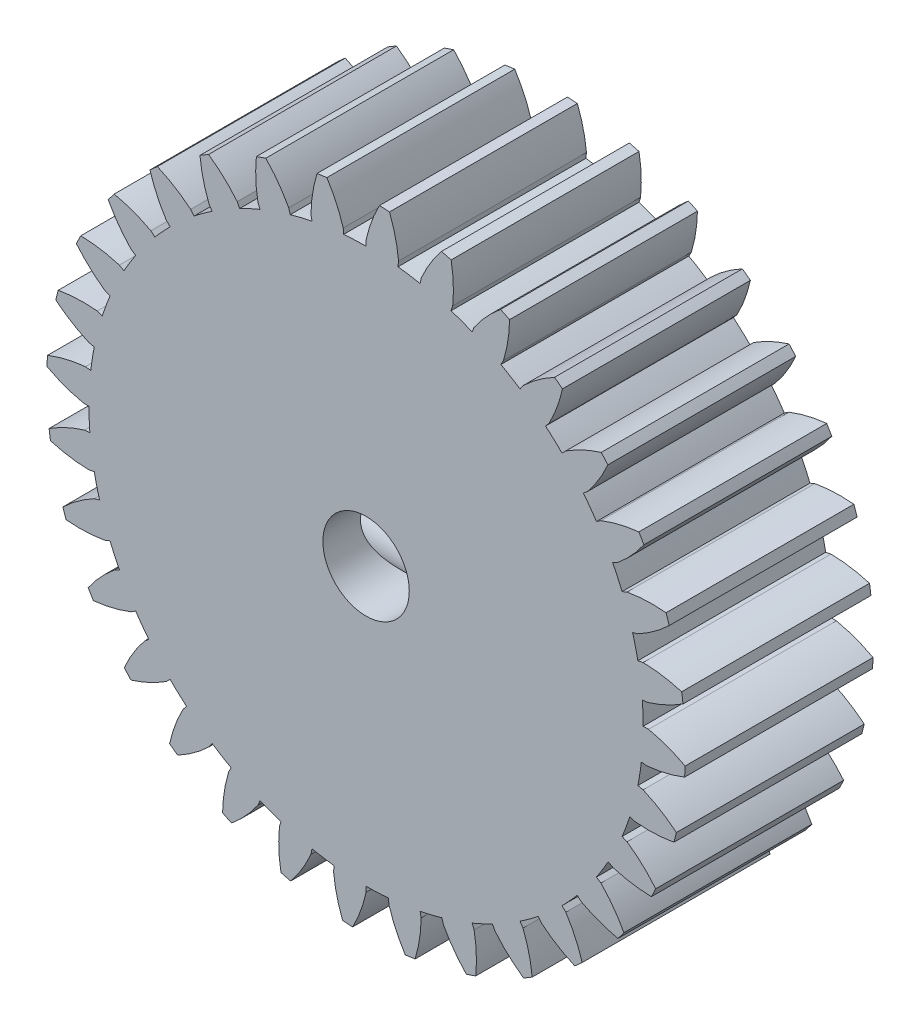
SolidWorks part; units mm, degrees
ref_plane "Front Plane" through (0, 0, 0) normal (0, 0, 1) x (1, 0, 0)
ref_plane "Top Plane" through (0, 0, 0) normal (0, 1, 0) x (1, 0, 0)
ref_plane "Right Plane" through (0, 0, 0) normal (1, 0, 0) x (0, 0, -1)
sketch "Gear" plane through (0, 0, 0) normal (0, 0, 1) x (1, 0, 0)
  circle A0 centre (0, 0) radius 8
  circle A1 centre (0, 0) radius 8.5
  circle A2 centre (0, 0) radius 7.375
  circle A3 centre (0, 0) radius 7.5
  circle A4 centre (0, 0) radius 7.5175
  dimension "Pitch" = 16
  dimension "Addendum" = 17
  dimension "Root" = 14.75
  dimension "Clearance" = 15
  dimension "Base" = 15.0351
sketch "Involute" plane through (0, 0, 0) normal (0, 0, 1) x (1, 0, 0)
  line L0 (0, 0) -> (0, 7.5175)
  line L1 (0, 0) -> (3.7588, 6.5104) construction
  line L2 (0, 0) -> (6.5104, 3.7588) construction
  line L3 (0, 0) -> (7.5175, 0) construction
  line L4 (7.5175, 0) -> (7.5175, 11.8085) construction
  line L5 (6.5104, 3.7588) -> (2.5742, 10.5764) construction
  line L6 (3.7588, 6.5104) -> (0.3499, 8.4785) construction
  line L7 (0, 0) -> (0.7841, 7.9615) construction
  line L8 (0, 0) -> (1.5607, 7.8463)
  line L9 (0.4614, 7.9867) -> (0, 0) construction
  circle A0 centre (0, 0) radius 7.5175 construction
  circle A1 centre (0, 0) radius 8 construction
  arc A3 (0.7841, 7.9615) -> (0.1378, 7.9988) centre (0, 0) ccw
  spline S0 degree 3 poles (0, 7.5175) (0.6613, 10.5961) (4.9807, 11.8125) (7.5175, 11.8085) knots 0 0 0 0 1 1 1 1
  spline S1 degree 3 poles (0.8656, 7.4675) (0.5632, 10.6018) (-3.5874, 12.3075) (-6.1078, 12.5956) knots 0 0 0 0 1 1 1 1
  point P10 (0, 0)
  dimension "Involute Control" = 90
  dimension "Base Circle Quarter Circumference" = 11.8085
  dimension "D1" = 7.8724
  dimension "D2" = 3.9362
  dimension "Circular Pitch" = 11.25
  dimension "Involute Array" = 4
sketch "Sketch3" plane through (0, 0, 0) normal (0, 0, 1) x (1, 0, 0)
  line L0 (0.8656, 7.4675) -> (0.8492, 7.3259)
  line L2 (0, 7.5175) -> (0, 7.375)
  arc A2 (0.3574, 8.4925) -> (0, 7.5175) centre (3.6484, 6.7332) ccw
  circle A10 centre (0, 0) radius 7.375 construction
  circle A11 centre (0, 0) radius 7.5175 construction
  arc A17 (0.8656, 7.4675) -> (0.6229, 8.4771) centre (-2.8488, 7.1085) ccw
  arc A18 (0.8492, 7.3259) -> (0, 7.375) centre (0, 0) ccw
  arc A19 (0.6229, 8.4771) -> (0.3574, 8.4925) centre (0, 0) ccw
  circle A20 centre (0, 0) radius 8.5 construction
  spline S1 degree 3 poles (0.8656, 7.4675) (0.5632, 10.6018) (-3.5874, 12.3075) (-6.1078, 12.5956) knots 0 0 0 0 1 1 1 1 construction
  spline S2 degree 3 poles (0, 7.5175) (0.6613, 10.5961) (4.9807, 11.8125) (7.5175, 11.8085) knots 0 0 0 0 1 1 1 1 construction
extrude "Boss-Extrude1" add sketch "Sketch3" along normal blind 5
ref_axis "Axis1" through (0, 0, 0) along (0, 0, 1)
pattern_circular "CirPattern1" count 32 over 360 about axis through (0, 0, 0) along (0, 0, 1) of bodies 101
sketch "Sketch6" plane through (0, 0, 0) normal (0, 0, 1) x (1, 0, 0)
  circle A0 centre (0, 0) radius 7.375 construction
  circle A1 centre (0, 0) radius 7.375
  circle A2 centre (0, 0) radius 1.15
  dimension "D1" = 2.3
extrude "Boss-Extrude3" add sketch "Sketch6" along normal up to surface (5 mm away) up to face at (-1.0773, 7.7198, 5)
sketch "Sketch9" plane through (0, 0, 0) normal (1, 0, 0) x (0, 0, -1)
  line L0 (-5, 8.4771) -> (0, 8.4771) construction
  circle A0 centre (-2.5, 0) radius 1.5
  point P8 (-2.5, 8.4771)
  dimension "D1" = 3
extrude "Cut-Extrude2" cut sketch "Sketch9" against normal blind 9
sketch "Sketch10" plane through (0, 0, 0) normal (1, 0, 0) x (0, 0, -1)
  line L0 (-5, 0) -> (0, 0) construction
  line L1 (-4, -1.5) -> (-1, -1.5)
  line L2 (-4, -1.5) -> (-4, 1.5)
  line L3 (-4, 1.5) -> (-1, 1.5)
  line L4 (-1, -1.5) -> (-1, 1.5)
  line L5 (-4, -1.5) -> (-1, 1.5) construction
  line L6 (-4, 1.5) -> (-1, -1.5) construction
  point P0 (-2.5, 0)
  dimension "D1" = 3
  dimension "D2" = 3
extrude "Cut-Extrude3" cut sketch "Sketch10" along direction (1, 0, 0) on the side of the normal up to surface (2.7792 mm away) from offset 10 up to face at (-7.1866, -1.6426, 2.4889) offset against normal yes
equation "\"Module\"= .5"
equation "\"Teeth\"= 32"
equation "\"Pressure Angle\"= 20deg"
equation "\"Pitch@Gear\"= \"Module\" * \"Teeth\""
equation "\"Addendum@Gear\" = \"Pitch@Gear\" +  ( \"Module\" * 2 ) "
equation "\"Clearance@Gear\" = \"Pitch@Gear\" - ( \"Module\" * 2 )"
equation "\"Root@Gear\"= \"Pitch@Gear\" - ( ( \"Module\" * 1.25 ) * 2 )"
equation "\"Base@Gear\"= \"Pitch@Gear\" * cos ( \"Pressure Angle\" )"
equation "\"Circular Pitch@Involute\"=360/\"Teeth\""
equation "\"Base Circle Quarter Circumference@Involute\"= \"Base@Gear\" * pi / 4"
equation "\"D1@Involute\"= \"Base Circle Quarter Circumference@Involute\" / 3 * 2"
equation "\"D2@Involute\"= \"Base Circle Quarter Circumference@Involute\" / 3"
equation "\"D1@CirPattern1\"= \"Teeth\""
